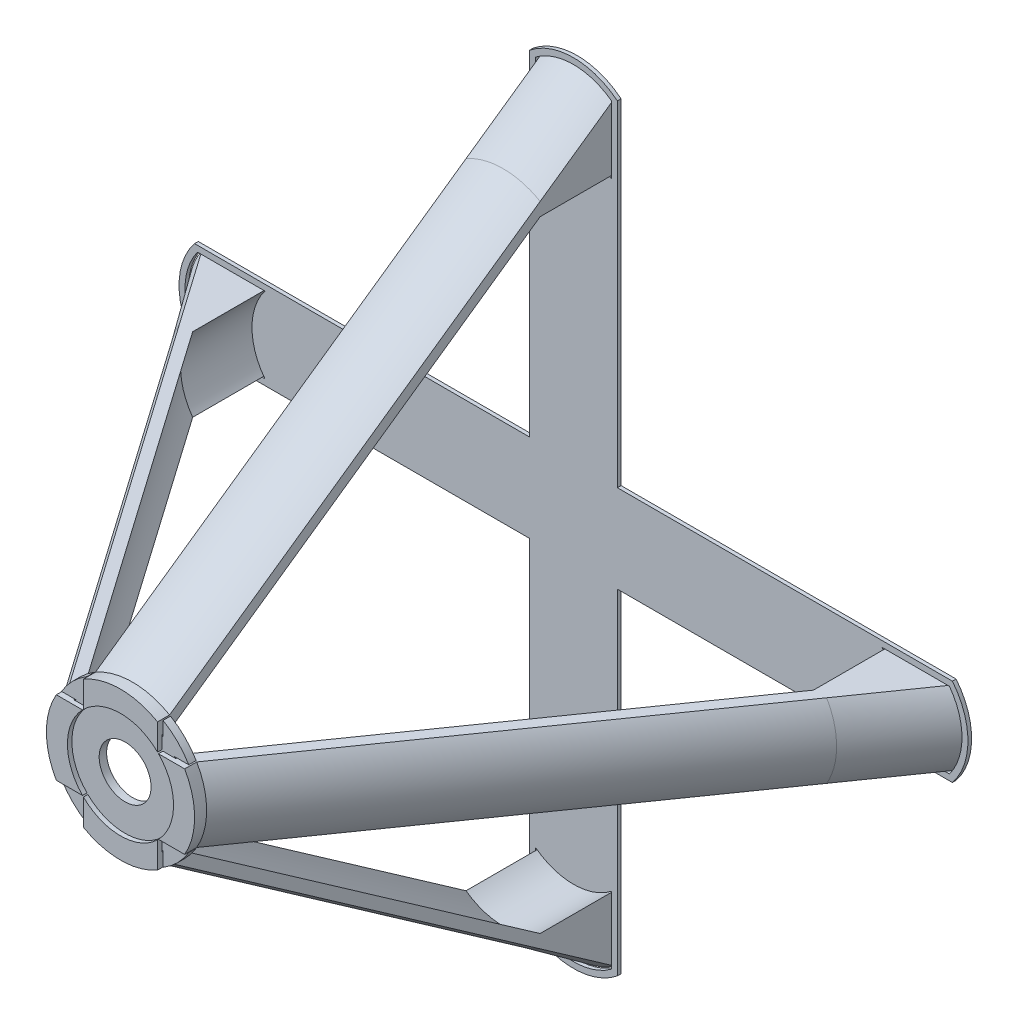
SolidWorks part; units mm, degrees
note: '?' marks a value the reader was unsure of. The reader was unsure of these and kept them because the rebuilt part matched: shared geometry of "Sketch4<2>".
ref_plane "Front" through (0, 0, 0) normal (0, 0, 1) x (1, 0, 0)
ref_plane "Top" through (0, 0, 0) normal (0, 1, 0) x (1, 0, 0)
ref_plane "Right" through (0, 0, 0) normal (1, 0, 0) x (0, 0, -1)
sketch "Sketch1" plane through (0, 0, 0) normal (0, 0, 1) x (1, 0, 0)
  circle A0 centre (0, 0) radius 20
  circle A1 centre (0, 0) radius 7
  dimension "D1" = 14
  dimension "D2" = 40
extrude "Boss-Extrude1" add sketch "Sketch1" along normal blind 2
sketch "Sketch2" plane through (0, 0, 0) normal (0, 1, 0) x (1, 0, 0)
  line L0 (-20, 0) -> (-90.0208, 100)
  line L1 (-20, 0) -> (0, 0) construction
  dimension "D1" = 55
  dimension "D2" = 100
sketch "Sketch3" plane through (0, 0, 0) normal (0, 0, -1) x (-1, 0, 0)
  line L0 (13.7477, -10) -> (17.3205, -10)
  line L1 (13.7477, 10) -> (17.3205, 10)
  arc A0 (13.7477, -10) -> (13.7477, 10) centre (0, 0) ccw
  circle A1 centre (0, 0) radius 20 construction
  arc A2 (17.3205, -10) -> (17.3205, 10) centre (0, 0) ccw
  point P4 (17, 0)
  dimension "D1" = 3
  dimension "D2" = 20
sweep "Sweep1" add profiles "Sketch3" path "Sketch2"
sketch "Sketch4" plane through (0, 0, -100) normal (0, 0, -1) x (-1, 0, 0)
  line L0 (87.3413, -10) -> (83.7685, -10)
  line L1 (87.3413, 10) -> (83.7685, 10)
  arc A0 (83.7685, -10) -> (83.7685, 10) centre (70.0208, 0) ccw
  arc A1 (83.7685, -10) -> (83.7685, 10) centre (70.0208, 0) ccw construction
  arc A2 (87.3413, -10) -> (87.3413, 10) centre (70.0208, 0) ccw
  arc A3 (87.3413, -10) -> (87.3413, 10) centre (70.0208, 0) ccw construction
extrude "Boss-Extrude3" add sketch "Sketch4" along normal blind 20
sketch "Sketch5" plane through (0, 0, 0) normal (0, 0, -1) x (-1, 0, 0)
  line L0 (17.3205, -10) -> (13.7477, -10)
  line L1 (17.3205, 10) -> (13.7477, 10)
  line L2 (17.4642, -10.25) -> (13.2476, -10.25)
  line L3 (17.4642, 10.25) -> (13.2476, 10.25)
  line L4 (-10, -17.3205) -> (-10, -13.7477)
  line L5 (10, -17.3205) -> (10, -13.7477)
  line L6 (-10.25, -17.4642) -> (-10.25, -13.2476)
  line L7 (10.25, -17.4642) -> (10.25, -13.2476)
  line L8 (-17.3205, 10) -> (-13.7477, 10)
  line L9 (-17.3205, -10) -> (-13.7477, -10)
  line L10 (-17.4642, 10.25) -> (-13.2476, 10.25)
  line L11 (-17.4642, -10.25) -> (-13.2476, -10.25)
  line L12 (10, 17.3205) -> (10, 13.7477)
  line L13 (-10, 17.3205) -> (-10, 13.7477)
  line L14 (10.25, 17.4642) -> (10.25, 13.2476)
  line L15 (-10.25, 17.4642) -> (-10.25, 13.2476)
  arc A0 (13.7477, 10) -> (13.7477, -10) centre (0, 0) cw
  arc A1 (13.7477, -10) -> (13.7477, 10) centre (0, 0) ccw construction
  arc A2 (17.3205, -10) -> (17.3205, 10) centre (0, 0) ccw
  arc A3 (17.3205, -10) -> (17.3205, 10) centre (0, 0) ccw construction
  arc A4 (13.2476, -10.25) -> (13.2476, 10.25) centre (0, 0) ccw
  arc A5 (17.4642, -10.25) -> (17.4642, 10.25) centre (0, 0) ccw
  arc A6 (10, -13.7477) -> (-10, -13.7477) centre (0, 0) cw
  arc A7 (-10, -17.3205) -> (10, -17.3205) centre (0, 0) ccw
  arc A8 (-10.25, -13.2476) -> (10.25, -13.2476) centre (0, 0) ccw
  arc A9 (-10.25, -17.4642) -> (10.25, -17.4642) centre (0, 0) ccw
  arc A10 (-13.7477, -10) -> (-13.7477, 10) centre (0, 0) cw
  arc A11 (-17.3205, 10) -> (-17.3205, -10) centre (0, 0) ccw
  arc A12 (-13.2476, 10.25) -> (-13.2476, -10.25) centre (0, 0) ccw
  arc A13 (-17.4642, 10.25) -> (-17.4642, -10.25) centre (0, 0) ccw
  arc A14 (-10, 13.7477) -> (10, 13.7477) centre (0, 0) cw
  arc A15 (10, 17.3205) -> (-10, 17.3205) centre (0, 0) ccw
  arc A16 (10.25, 13.2476) -> (-10.25, 13.2476) centre (0, 0) ccw
  arc A17 (10.25, 17.4642) -> (-10.25, 17.4642) centre (0, 0) ccw
  point P49 (0, 0)
  dimension "D3" = 0.25
  dimension "D4" = 0.25
  dimension "D1" = 0.25
  dimension "D2" = 0.25
  dimension "D5" = 4
extrude "Cut-Extrude1" cut sketch "Sketch5" against normal through all
sketch "Sketch6" plane through (0, 0, 2) normal (0, 0, 1) x (1, 0, 0)
  line L0 (-17.3205, 10) -> (-13.7477, 10)
  line L1 (-17.3205, -10) -> (-13.7477, -10)
  arc A0 (-17.3205, 10) -> (-17.3205, -10) centre (0, 0) ccw
  arc A1 (-17.3205, 10) -> (-17.3205, -10) centre (0, 0) ccw construction
  arc A2 (-13.7477, -10) -> (-13.7477, 10) centre (0, 0) cw
  arc A3 (-13.7477, 10) -> (-13.7477, -10) centre (0, 0) ccw construction
extrude "Boss-Extrude4" add sketch "Sketch6" along normal blind 1.25
sketch "Sketch7" plane through (0, 0, 3.25) normal (0, 0, 1) x (1, 0, 0)
  line L0 (-13.7477, 10) -> (-10.25, 10)
  line L1 (-13.7477, -10) -> (-10.25, -10)
  line L2 (-10.25, -17.1737) -> (-10.25, -13.2476) construction
  arc A0 (-13.7477, 10) -> (-13.7477, -10) centre (0, 0) ccw
  arc A1 (-13.7477, 10) -> (-13.7477, -10) centre (0, 0) ccw construction
  arc A2 (-10.25, 10) -> (-10.25, -10) centre (0, 0) ccw
extrude "Boss-Extrude5" add sketch "Sketch7" against normal blind 1.2
ref_point "Point1"
ref_axis "Axis3" through (-101.3454, -10, -120) along (0, 0, -1)?
sketch "Sketch9" plane through (0, 0, -120) normal (0, 0, -1) x (-1, 0, 0)
  line L0 (83.7685, -10) -> (101.3454, -10)
  line L1 (83.7685, 10) -> (101.3454, 10)
  arc A0 (83.7685, 10) -> (83.7685, -10) centre (70.0208, 0) cw
  arc A1 (83.7685, -10) -> (83.7685, 10) centre (70.0208, 0) ccw construction
  arc A2 (101.3454, -10) -> (101.3454, 10) centre (87.5977, 0) ccw
loft "Loft1" add profiles "Sketch9", "Sketch4<2>"
sketch "Sketch4<2>" plane through (0, 0, -100) normal (0, 0, -1) x (-1, 0, 0) same geometry as "Sketch4"
pattern_circular "CirPattern3" count 4 over 360 of bodies 112
sketch "Sketch10" plane through (0, 0, -120) normal (0, 0, -1) x (-1, 0, 0)
  line L0 (11.85, -102.2572) -> (11.85, -11.85)
  line L1 (11.85, -11.85) -> (102.2572, -11.85)
  line L2 (-11.85, -102.2572) -> (-11.85, -11.85)
  line L3 (-11.85, -11.85) -> (-102.2572, -11.85)
  line L4 (102.2572, 11.85) -> (11.85, 11.85)
  line L5 (11.85, 11.85) -> (11.85, 102.2572)
  line L6 (-11.85, 102.2572) -> (-11.85, 11.85)
  line L7 (-11.85, 11.85) -> (-102.2572, 11.85)
  line L8 (101.4721, 10.25) -> (83.2684, 10.25)
  line L9 (101.4721, -10.25) -> (83.2684, -10.25)
  line L10 (87.3413, -10) -> (101.3454, -10) construction
  line L11 (101.3454, 10) -> (87.3413, 10) construction
  line L12 (-10.25, -101.4721) -> (-10.25, -83.2684)
  line L13 (10.25, -101.4721) -> (10.25, -83.2684)
  line L14 (-101.4721, 10.25) -> (-83.2684, 10.25)
  line L15 (-101.4721, -10.25) -> (-83.2684, -10.25)
  line L16 (10.25, 101.4721) -> (10.25, 83.2684)
  line L17 (-10.25, 101.4721) -> (-10.25, 83.2684)
  arc A0 (102.2572, 11.85) -> (102.2572, -11.85) centre (87.5977, 0) cw
  arc A1 (101.3454, -10) -> (101.3454, 10) centre (87.5977, 0) ccw construction
  arc A2 (101.4721, 10.25) -> (101.4721, -10.25) centre (87.5977, 0) cw
  arc A3 (10.25, -101.4721) -> (-10.25, -101.4721) centre (0, -87.5977) cw
  arc A4 (83.7685, -10) -> (83.7685, 10) centre (70.0208, 0) ccw construction
  arc A5 (10.25, -83.2684) -> (-10.25, -83.2684) centre (0, -70.0208) cw
  arc A6 (83.2684, 10.25) -> (83.2684, -10.25) centre (70.0208, 0) cw
  arc A7 (-101.4721, -10.25) -> (-101.4721, 10.25) centre (-87.5977, 0) cw
  arc A8 (-83.2684, -10.25) -> (-83.2684, 10.25) centre (-70.0208, 0) cw
  arc A9 (-10.25, 101.4721) -> (10.25, 101.4721) centre (0, 87.5977) cw
  arc A10 (-10.25, 83.2684) -> (10.25, 83.2684) centre (0, 70.0208) cw
  arc A11 (11.85, -102.2572) -> (-11.85, -102.2572) centre (0, -87.5977) cw
  arc A12 (-102.2572, -11.85) -> (-102.2572, 11.85) centre (-87.5977, 0) cw
  arc A13 (-11.85, 102.2572) -> (11.85, 102.2572) centre (0, 87.5977) cw
  point P49 (0, 0)
  point P59 (0, 0)
  dimension "D1" = 0.25
  dimension "D4" = 0.25
  dimension "D6" = 1.6
  dimension "D2" = 0.25
  dimension "D3" = 0.25
  dimension "D5" = 1.6
  dimension "D7" = 1.6
  dimension "D8" = 4
  dimension "D9" = 4
extrude "Boss-Extrude6" add sketch "Sketch10" against normal blind 1 separate body
